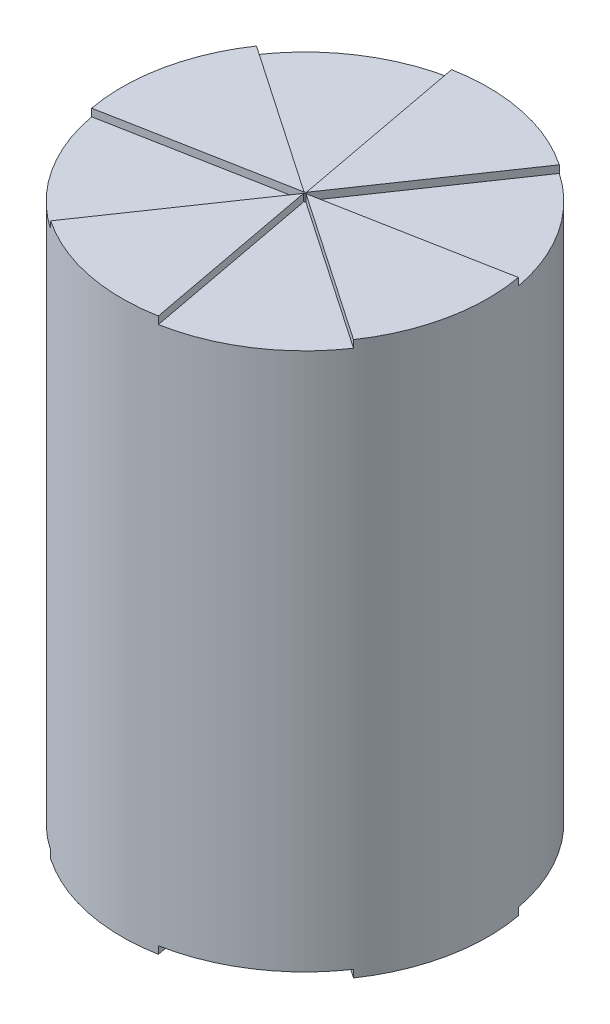
SolidWorks part; units mm, degrees
material "Nylon 101"
ref_plane "Front" through (0, 0, 0) normal (0, 0, 1) x (1, 0, 0)
ref_plane "Top" through (0, 0, 0) normal (0, 1, 0) x (1, 0, 0)
ref_plane "Right" through (0, 0, 0) normal (1, 0, 0) x (0, 0, -1)
sketch "Sketch1" plane through (0, 0, 0) normal (0, 1, 0) x (1, 0, 0)
  circle A0 centre (0, 0) radius 62.23
  dimension "D1" = 124.46
extrude "Boss-Extrude1" add sketch "Sketch1" along normal blind 187.96
sketch "Sketch2" plane through (0, 187.96, 0) normal (0, 1, 0) x (1, 0, 0)
  line L6 (-34.9778, -51.4697) -> (0.0216, -0.2531)
  line L7 (-0.2231, 0.1215) -> (-61.187, -11.3458)
  arc A6 (-34.9778, -51.4697) -> (-61.187, -11.3458) centre (0, 0) cw
  arc A7 (0.0216, -0.2531) -> (-0.2231, 0.1215) centre (0, 0) cw
  circle A8 centre (0, 0) radius 62.23 construction
  dimension "D1" = 45
  dimension "D3" = 62.033
  dimension "D2" = 0.254
extrude "Cut-Extrude7" cut sketch "Sketch2" against normal blind 2.54
pattern_circular "CirPattern2" count 4 over 360 about axis through (0, 187.96, 0) along (0, 1, 0) of "Cut-Extrude7"
ref_plane "Plane1" through (0, 93.98, 0) normal (0, 1, 0) x (1, 0, 0)
mirror "Mirror1" about plane through (0, 93.98, 0) normal (0, 1, 0) of "CirPattern2"
